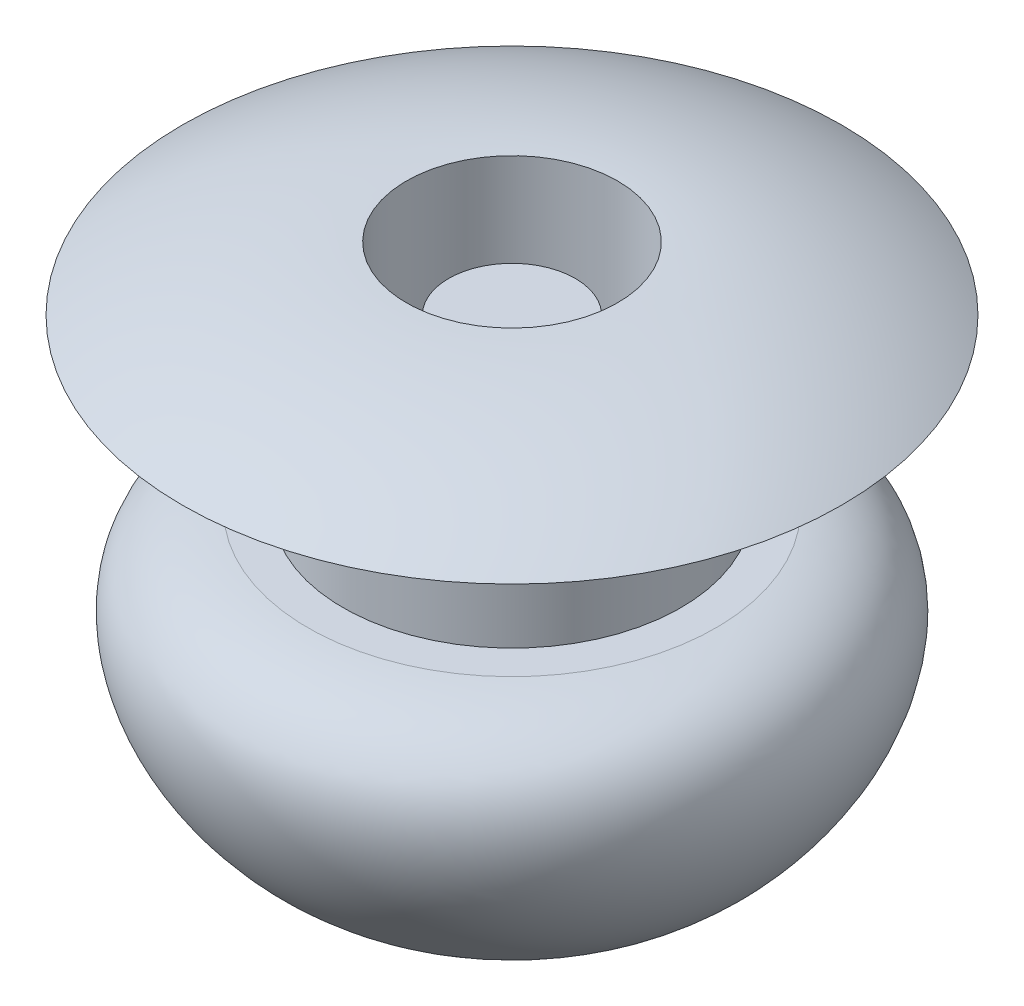
SolidWorks part; units mm, degrees
material "AISI 316 Stal nierdzewna odprężona (SS)"
ref_plane "Płaszczyzna przednia" through (0, 0, 0) normal (0, 0, 1) x (1, 0, 0)
ref_plane "Płaszczyzna górna" through (0, 0, 0) normal (0, 1, 0) x (1, 0, 0)
ref_plane "Płaszczyzna prawa" through (0, 0, 0) normal (1, 0, 0) x (0, 0, -1)
sketch "Szkic1" plane through (0, 0, 0) normal (1, 0, 0) x (0, 0, -1)
  line L0 (0, 0) -> (0, -2)
  line L1 (0, 0) -> (-0.75, 0)
  line L2 (-0.75, 0) -> (-0.75, -2)
  line L3 (-0.75, -2) -> (-1.25, -2)
  line L4 (-1.25, -2) -> (-1.25, 0.75)
  line L5 (-3.9, 0) -> (-2, 0)
  line L6 (-2, 0) -> (-2, -2)
  line L7 (-2, -2) -> (-2.4139, -2)
  line L8 (0, 0) -> (0, 0.4842) construction
  line L10 (0, -2) -> (0, -3.5)
  line L11 (-573, -2) -> (7, -2) construction
  arc A0 (-1.25, 0.75) -> (-3.9, 0) centre (-1.25, -4.3067) ccw
  ellipse E0 centre (0, -2.75) end of major axis (1.75, -2.75) minor radius 0.75 (-0.956, -3.3782) -> (0, -3.5) ccw
  spline S0 degree 3 poles (-2.4139, -2) (-3.8586, -2.1633) (-3.5584, -4.323) (-0.9713, -5.8719) (-0.3411, -3.792) (-0.956, -3.3782) knots 0 0 0 0 0.454219 0.705201 1 1 1 1
  point P25 (-2.2069, -2)
  dimension "D1" = 7.8
  dimension "D2" = 2.5
  dimension "D3" = 4
  dimension "D4" = 0.75
  dimension "D5" = 1.5
  dimension "D6" = 1.5
  dimension "D7" = 3.5
  dimension "D8" = 3.1855
  dimension "D9" = 2.5026
  dimension "D10" = 1.9
  dimension "D11" = 1.3782
  dimension "D12" = 0.5792
  dimension "D13" = 4.8278
  dimension "D14" = 3.3858
  dimension "D15" = 2.8395
  dimension "D16" = 1.25
  dimension "D17" = 0.6409
  dimension "D18" = 0.956
revolve "Obrót1" add sketch "Szkic1" angle 360 about L8
